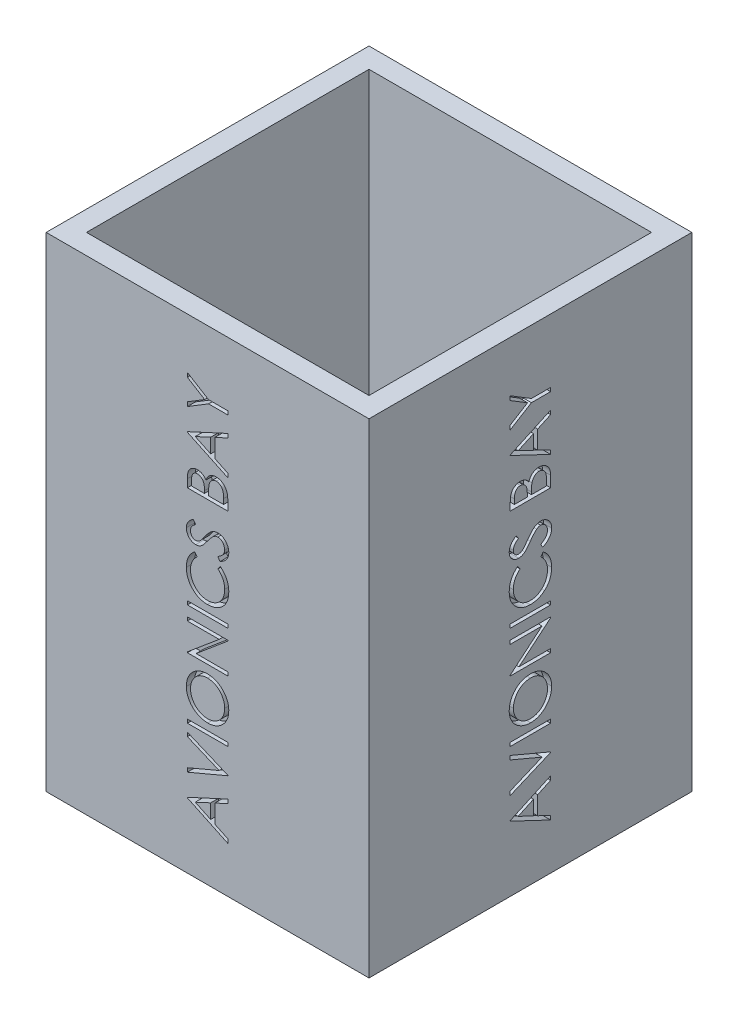
SolidWorks part; units mm, degrees
material "PVC Rigid"
ref_plane "Front Plane" through (0, 0, 0) normal (0, 0, 1) x (1, 0, 0)
ref_plane "Top Plane" through (0, 0, 0) normal (0, 1, 0) x (1, 0, 0)
ref_plane "Right Plane" through (0, 0, 0) normal (1, 0, 0) x (0, 0, -1)
sketch "Sketch1" plane through (0, 0, 0) normal (0, 1, 0) x (1, 0, 0)
  line L1 (-50.8, -50.8) -> (50.8, -50.8)
  line L2 (-50.8, -50.8) -> (-50.8, 50.8)
  line L3 (-50.8, 50.8) -> (50.8, 50.8)
  line L4 (50.8, -50.8) -> (50.8, 50.8)
  line L5 (-50.8, -50.8) -> (50.8, 50.8) construction
  line L6 (-50.8, 50.8) -> (50.8, -50.8) construction
  line L7 (-44.45, -44.45) -> (44.45, -44.45)
  line L8 (-44.45, -44.45) -> (-44.45, 44.45)
  line L9 (-44.45, 44.45) -> (44.45, 44.45)
  line L10 (44.45, -44.45) -> (44.45, 44.45)
  line L11 (-44.45, -44.45) -> (44.45, 44.45) construction
  line L12 (-44.45, 44.45) -> (44.45, -44.45) construction
  point P0 (0, 0)
  point P6 (0, 0)
  dimension "D1" = 101.6
  dimension "D2" = 101.6
  dimension "D3" = 88.9
extrude "Boss-Extrude1" add sketch "Sketch1" along normal blind 152.4
sketch "Sketch6" plane through (-50.8, 0, 0) normal (-1, 0, 0) x (0, 0, 1)
  line L0 (6.35, 0) -> (6.35, 152.4) construction
  line L1 (-50.8, 0) -> (50.8, 0) construction
  line L2 (-50.8, 152.4) -> (50.8, 152.4) construction
  line L3 (-50.8, 152.4) -> (-50.8, 0) construction
  text T0 "AVIONICS BAY" font "Century Gothic" height in points 48
  dimension "D1" = 57.15
extrude "Cut-Extrude1" cut sketch "Sketch6" against normal blind 2.54
sketch "Sketch7" plane through (0, 0, 0) normal (0, 0, 1) x (1, 0, 0)
  line L0 (0, 0) -> (0, 152.4) construction
  line L1 (-50.8, 152.4) -> (50.8, 152.4) construction
pattern_circular "CirPattern1" count 4 over 360 about axis through (0, 0, 0) along (0, 1, 0) of "Cut-Extrude1" reverse direction yes
